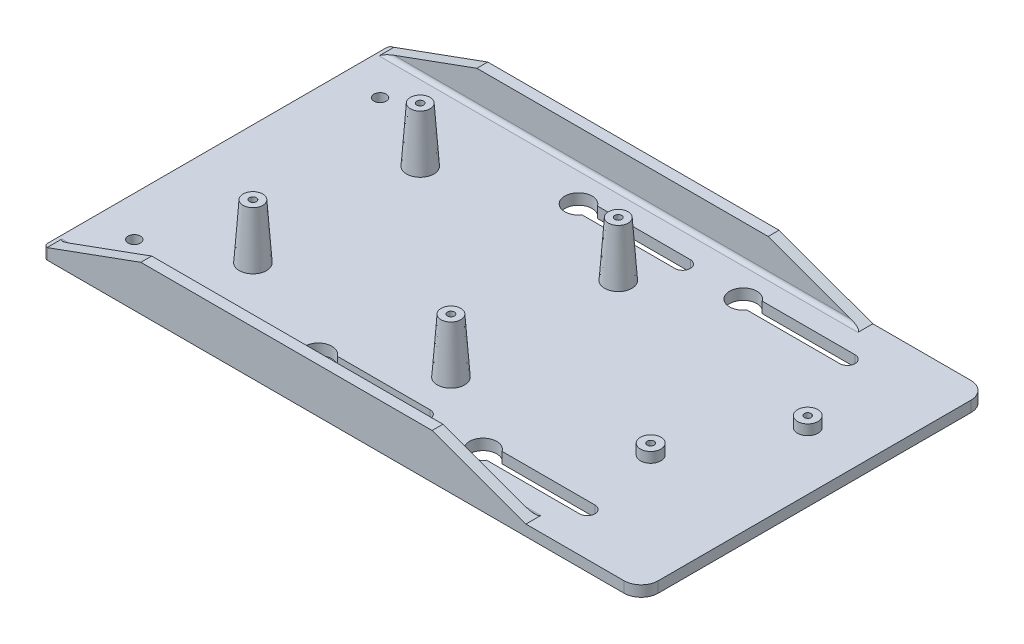
SolidWorks part; units mm, degrees
ref_plane "Front Plane" through (0, 0, 0) normal (0, 0, 1) x (1, 0, 0)
ref_plane "Top Plane" through (0, 0, 0) normal (0, 1, 0) x (1, 0, 0)
ref_plane "Right Plane" through (0, 0, 0) normal (1, 0, 0) x (0, 0, -1)
sketch "Sketch1" plane through (0, 0, 0) normal (0, 1, 0) x (1, 0, 0)
  line L0 (0, 0) -> (175, 0) construction
  line L1 (0, 50.8) -> (175, 50.8)
  line L2 (0, 50.8) -> (0, -50.8)
  line L3 (0, -50.8) -> (175, -50.8)
  line L4 (175, 50.8) -> (175, -50.8)
  line L5 (0, 50.8) -> (175, -50.8) construction
  line L6 (0, -50.8) -> (175, 50.8) construction
  point P0 (11.3289, 32.4526)
  point P5 (0, 0)
  dimension "D1" = 101.6
  dimension "D2" = 175
extrude "plate" add sketch "Sketch1" along normal blind 3.175
sketch "Sketch14" plane through (0, 0, 0) normal (0, -1, 0) x (1, 0, 0)
  text T0 "BOTTOM" font "Century Gothic" height 3.5
extrude "bottom label" cut sketch "Sketch14" against normal blind 0.6
hole_wizard "mount slots" positions "Sketch8" profile "Sketch9" size "M4" standard "ISO" slot yes end condition through all
sketch "Sketch8" plane through (0, 3.175, 0) normal (0, 1, 0) x (1, 0, 0)
  line L0 (83, 38.1) -> (131.26, 38.1) construction
  line L2 (0, 0) -> (175, 0) construction
  line L3 (175, -50.8) -> (175, 50.8) construction
  line L4 (0, 50.8) -> (0, -50.8) construction
  line L5 (83, -38.1) -> (131.26, -38.1) construction
  line L6 (65.5, 38.1) -> (100.5, 38.1) construction
  point P1 (83, 38.1)
  point P2 (131.26, 38.1)
  point P23 (131.26, -38.1)
  point P24 (83, -38.1)
  dimension "D1" = 48.26
  dimension "D2" = 38.1
  dimension "D3" = 83
  dimension "D4" = 35
sketch "Sketch9" plane through (83, 3.175, -38.1) normal (1, 0, 0) x (0, 0, 1)
  line L0 (0, 0) -> (0, 3.175)
  line L1 (0, 3.175) -> (2.25, 3.175)
  line L2 (2.25, 3.175) -> (2.25, 0)
  line L5 (2.25, 0) -> (0, 0)
  line L11 (0, -6.35) -> (0, 107.95) construction
  dimension "Thru Hole Dia." = 4.5
  dimension "Thru Hole Depth" = 3.175
sketch "Sketch12" plane through (0, 3.175, 0) normal (0, 1, 0) x (1, 0, 0)
  line L0 (-1.7462, 0) -> (1.7462, 0) construction
  circle A0 centre (116.01, 38.1) radius 4
  circle A1 centre (67.75, 38.1) radius 4
  circle A5 centre (67.75, -38.1) radius 4
  circle A6 centre (116.01, -38.1) radius 4
  arc A7 (67.75, 40.35) -> (67.75, 35.85) centre (67.75, 38.1) ccw construction
  arc A8 (116.01, 40.35) -> (116.01, 35.85) centre (116.01, 38.1) ccw construction
  dimension "D1" = 8
  dimension "D2" = 8
extrude "slot_clearance" cut sketch "Sketch12" against normal through all
hole_wizard "bracket  holes" positions "Sketch10" profile "Sketch11" hole size "M3" standard "ISO" end condition through all
sketch "Sketch10" plane through (0, 3.175, 0) normal (0, 1, 0) x (1, 0, 0)
  line L0 (0, 0) -> (175, 0) construction
  line L1 (0, 50.8) -> (0, -50.8) construction
  line L2 (175, -50.8) -> (175, 50.8) construction
  point P0 (11.75, 36)
  point P14 (11.75, -36)
  dimension "D1" = 11.75
  dimension "D2" = 36
sketch "Sketch11" plane through (11.75, 3.175, -36) normal (1, 0, 0) x (0, 0, 1)
  line L0 (0, 0) -> (0, 3.175)
  line L1 (0, 3.175) -> (1.8, 3.175)
  line L2 (1.8, 3.175) -> (1.8, 0)
  line L5 (1.8, 0) -> (0, 0)
  line L11 (0, -6.35) -> (0, 107.95) construction
  dimension "Thru Hole Dia." = 3.6
  dimension "Thru Hole Depth" = 3.175
sketch "Sketch13" plane through (0, 0, -50.8) normal (0, 0, -1) x (-1, 0, 0)
  line L0 (-141.26, 3.175) -> (-113.7852, 13.175)
  line L1 (-175, 3.175) -> (0, 3.175) construction
  line L2 (-113.7852, 13.175) -> (-28.4748, 13.175)
  line L3 (-28.4748, 13.175) -> (-1, 3.175)
  line L4 (-1, 3.175) -> (-141.26, 3.175)
  line L6 (0, 3.175) -> (0, 0) construction
  point P10 (0, 1.5875)
  dimension "D1" = 20
  dimension "D2" = 10
  dimension "D3" = 20
  dimension "D4" = 1
  dimension "D5" = 10
extrude "plate stiffener" add sketch "Sketch13" against normal blind 3.175
mirror "stiffener mirror" about plane through (0, 0, 0) normal (0, 0, 1) of "plate stiffener"
sketch "Sketch15" plane through (0, 3.175, 0) normal (0, 1, 0) x (1, 0, 0)
  line L1 (0, 0) -> (102.1318, 0) construction
  line L2 (64, 24.5) -> (64, 0) construction
  line L3 (35, 24.5) -> (93, 24.5) construction
  line L4 (-7.2462, 0) -> (7.2462, 0) construction
  circle A1 centre (93, 24.5) radius 4
  circle A2 centre (35, 24.5) radius 4
  circle A3 centre (35, -24.5) radius 4
  circle A4 centre (93, -24.5) radius 4
  dimension "D1" = 8
  dimension "D4" = 58
  dimension "D2" = 35
  dimension "D3" = 24.5
extrude "pi standoffs" add sketch "Sketch15" along normal blind 16 draft 4
hole_wizard "pi hole M2.5 tapped" positions "Sketch18" profile "Sketch19" hole size "M2.5" standard "ISO" end condition through all
sketch "Sketch18" plane through (0, 19.175, 0) normal (0, 1, 0) x (1, 0, 0)
  circle A0 centre (93, -24.5) radius 2.8812 construction
  circle A1 centre (35, -24.5) radius 2.8812 construction
  circle A2 centre (35, 24.5) radius 2.8812 construction
  circle A3 centre (93, 24.5) radius 2.8812 construction
  point P0 (35, -24.5)
  point P2 (35, 24.5)
  point P4 (93, 24.5)
  point P6 (93, -24.5)
sketch "Sketch19" plane through (35, 19.175, 24.5) normal (1, 0, 0) x (0, 0, 1)
  line L0 (0, 0) -> (0, 19.175)
  line L1 (0, 19.175) -> (1.025, 19.175)
  line L2 (1.025, 19.175) -> (1.025, 0)
  line L5 (1.025, 0) -> (0, 0)
  line L11 (0, -6.35) -> (0, 107.95) construction
  dimension "Thru Hole Dia." = 2.05
  dimension "Thru Hole Depth" = 19.175
sketch "Sketch20" plane through (0, 3.175, 0) normal (0, 1, 0) x (1, 0, 0)
  line L0 (0, 0) -> (175, 0) construction
  line L1 (142, -15) -> (158, -15) construction
  line L2 (142, -15) -> (142, 15) construction
  line L3 (142, 15) -> (158, 15) construction
  line L4 (158, -15) -> (158, 15) construction
  line L5 (0, 50.8) -> (0, -50.8) construction
  line L7 (175, -50.8) -> (175, 50.8) construction
  circle A0 centre (158, 15) radius 3
  circle A1 centre (142, -15) radius 3
  point P0 (158, 15)
  point P1 (142, -15)
  point P8 (142, 0)
  point P9 (158, 0)
  dimension "D4" = 6
  dimension "D5" = 6
  dimension "D1" = 16
  dimension "D2" = 30
  dimension "D3" = 142
extrude "reg standoffs" add sketch "Sketch20" along normal blind 3
hole_wizard "reg hole M2.5 tapped" positions "Sketch21" profile "Sketch22" hole size "M2.5" standard "ISO" end condition through all
sketch "Sketch21" plane through (0, 6.175, 0) normal (0, 1, 0) x (1, 0, 0)
  circle A0 centre (158, 15) radius 3 construction
  circle A1 centre (142, -15) radius 3 construction
  point P0 (142, -15)
  point P2 (158, 15)
sketch "Sketch22" plane through (142, 6.175, 15) normal (1, 0, 0) x (0, 0, 1)
  line L0 (0, 0) -> (0, 6.175)
  line L1 (0, 6.175) -> (1.025, 6.175)
  line L2 (1.025, 6.175) -> (1.025, 0)
  line L5 (1.025, 0) -> (0, 0)
  line L11 (0, -6.35) -> (0, 107.95) construction
  dimension "Thru Hole Dia." = 2.05
  dimension "Thru Hole Depth" = 6.175
fillet "Fillet 1.2mm" radius 1.2 4 edges at (71.13, 3.175, 47.625) (71.13, 3.175, -47.625) (0, 1.5875, -50.8) (0, 1.5875, 50.8)
fillet "Fillet2" radius 5 2 edges at (175, 1.5875, 50.8) (175, 1.5875, -50.8)
